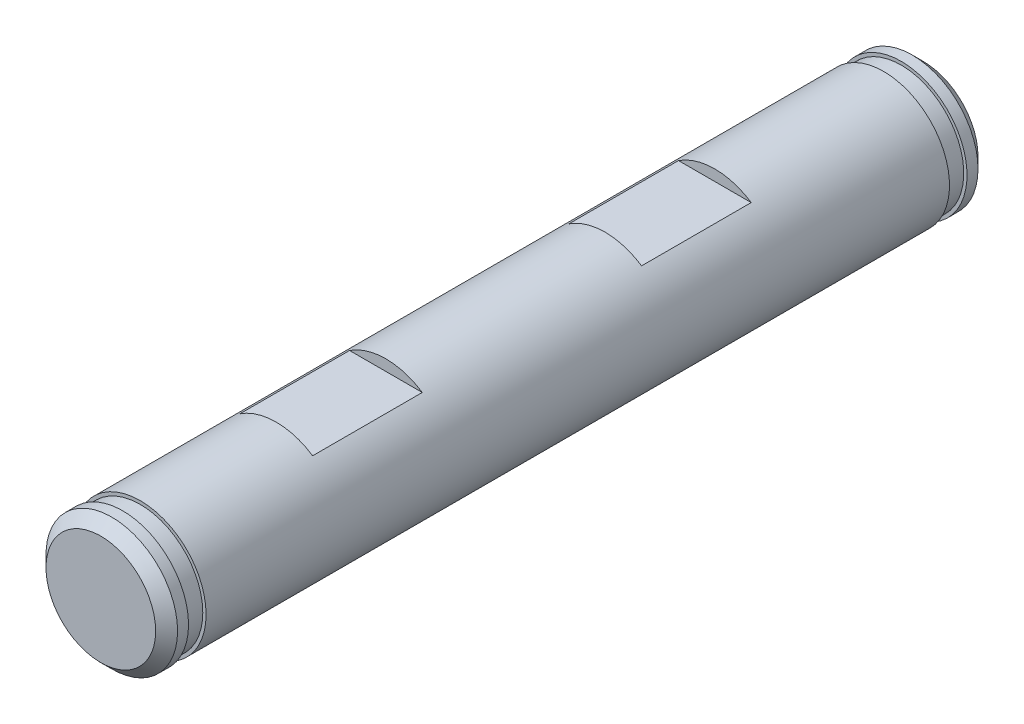
SolidWorks part; units mm, degrees
material "Stop 1060"
ref_plane "Płaszczyzna przednia" through (0, 0, 0) normal (0, 0, 1) x (1, 0, 0)
ref_plane "Płaszczyzna górna" through (0, 0, 0) normal (0, 1, 0) x (1, 0, 0)
ref_plane "Płaszczyzna prawa" through (0, 0, 0) normal (1, 0, 0) x (0, 0, -1)
sketch "Szkic1" plane through (0, 0, 0) normal (0, 0, 1) x (1, 0, 0)
  circle A0 centre (0, 0) radius 3
  dimension "D1" = 6
extrude "Dodanie-wyciągnięcie1" add sketch "Szkic1" along normal blind 37.5
chamfer "Sfazowanie1" distance 0.5 angle 45 2 edges at (3, 0, 0) (3, 0, 37.5)
sketch "Szkic2" plane through (0, 0, 37.5) normal (0, 0, 1) x (1, 0, 0)
  circle A0 centre (0, 0) radius 3
  circle A1 centre (0, 0) radius 2.85
  dimension "D1" = 6
  dimension "D2" = 5.7
extrude "Wytnij-wyciągnięcie1" cut sketch "Szkic2" against normal blind 0.8 from offset 1 offset against normal yes
sketch "Szkic3" plane through (0, 0, 0) normal (0, 0, -1) x (-1, 0, 0)
  circle A0 centre (0, 0) radius 3
  circle A1 centre (0, 0) radius 2.85
  dimension "D1" = 5.7
  dimension "D2" = 6
extrude "Wytnij-wyciągnięcie2" cut sketch "Szkic3" against normal blind 0.8 from offset 1 offset against normal yes
sketch "Szkic4" plane through (0, 0, 37.5) normal (0, 0, 1) x (1, 0, 0)
  line L0 (-1.6583, 2.5) -> (1.6583, 2.5)
  arc A0 (1.6583, 2.5) -> (-1.6583, 2.5) centre (0, 0) ccw
  dimension "D1" = 6
  dimension "D2" = 2.5
extrude "Wytnij-wyciągnięcie3" cut sketch "Szkic4" along normal blind 5 from offset 13 offset against normal yes
extrude "Wytnij-wyciągnięcie4" cut sketch "Szkic4<2>" against normal blind 5 from offset 23 offset against normal yes
sketch "Szkic4<2>" plane through (0, 0, 37.5) normal (0, 0, 1) x (1, 0, 0) same geometry as "Szkic4"
